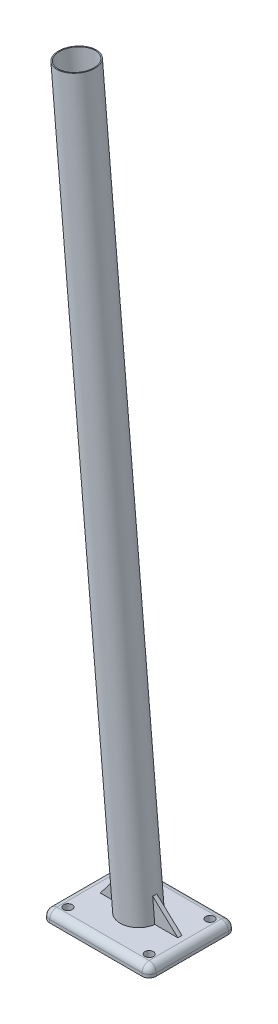
SolidWorks part; units mm, degrees
ref_plane "Front Plane" through (0, 0, 0) normal (0, 0, 1) x (1, 0, 0)
ref_plane "Top Plane" through (0, 0, 0) normal (0, 1, 0) x (1, 0, 0)
ref_plane "Right Plane" through (0, 0, 0) normal (1, 0, 0) x (0, 0, -1)
sketch "Sketch1" plane through (0, 0, 0) normal (0, 1, 0) x (1, 0, 0)
  line L1 (52.5, -42.5) -> (-52.5, -42.5)
  line L2 (52.5, -42.5) -> (52.5, 42.5)
  line L3 (52.5, 42.5) -> (-52.5, 42.5)
  line L4 (-52.5, -42.5) -> (-52.5, 42.5)
  line L5 (52.5, -42.5) -> (-52.5, 42.5) construction
  line L6 (52.5, 42.5) -> (-52.5, -42.5) construction
  line L7 (40, -30) -> (-40, -30) construction
  line L8 (40, -30) -> (40, 30) construction
  line L9 (40, 30) -> (-40, 30) construction
  line L10 (-40, -30) -> (-40, 30) construction
  line L11 (40, -30) -> (-40, 30) construction
  line L12 (40, 30) -> (-40, -30) construction
  circle A2 centre (-40, -30) radius 4.2
  circle A3 centre (40, 30) radius 4.2
  circle A4 centre (40, -30) radius 4.2
  circle A5 centre (-40, 30) radius 4.2
  point P0 (0, 0)
  point P6 (0, 0)
  dimension "D3" = 60
  dimension "D5" = 8.4
  dimension "D1" = 85
  dimension "D2" = 105
  dimension "D4" = 80
extrude "Boss-Extrude1" add sketch "Sketch1" along normal blind 10
sketch "Sketch5" plane through (0, 0, 0) normal (0, 0, 1) x (1, 0, 0)
  line L0 (0, 99.305) -> (0, -31.2001) construction
  line L2 (-7.9994, 101.4331) -> (0, 10)
  line L3 (-52.5, 10) -> (52.5, 10) construction
  dimension "D1" = 85
ref_plane "Plane1" through (0, 10, 0) normal (0.0872, -0.9962, 0) x (-0.9962, -0.0872, 0)
sketch "Sketch14" plane through (0, 10, 0) normal (0.0872, -0.9962, 0) x (-0.9962, -0.0872, 0)
  line L0 (-7.7834, 0) -> (3.5908, 0) construction
  line L1 (-51.4287, -42.5) -> (52.3002, 42.5) construction
  line L2 (-51.4287, 42.5) -> (52.3002, -42.5) construction
  circle A0 centre (0.4358, 0) radius 18
  circle A1 centre (0.4358, 0) radius 17
  dimension "D1" = 36
  dimension "D3" = 0
  dimension "D2" = 34
extrude "Boss-Extrude4" add sketch "Sketch14" against normal blind 700 and the other way up to surface other way up to face at (40, 10, 34.2)
sketch "Sketch16" plane through (0, 0, 0) normal (0, 0, 1) x (1, 0, 0)
  line L0 (36.0762, 10.055) -> (-3.0211, 63.3047)
ref_plane "Plane2" through (-52.5, 10, 42.5) normal (1, 0, 0) x (0, 0, -1)
sketch "Sketch21" plane through (0, 0, 0) normal (0, 0, 1) x (1, 0, 0)
  line L0 (15.616, 33.0356) -> (40.2682, 10)
  line L1 (17.6313, 10) -> (-43.5116, 708.8671) construction
  line L2 (-52.5, 10) -> (52.5, 10) construction
rib "Rib2" sketch "Sketch21" sketch "Sketch21" thickness 4 extrusion direction parallel to sketch draft on no parameters "D1"=4
sketch "Sketch22" plane through (0, 0, 0) normal (0, 0, 1) x (1, 0, 0)
  line L0 (-20.3162, 30.6879) -> (-36.1382, 10)
  line L1 (-79.3746, 705.7295) -> (-18.5062, 10) construction
  line L2 (-52.5, 10) -> (52.5, 10) construction
rib "Rib5" sketch "Sketch22" sketch "Sketch22" thickness 4 extrusion direction parallel to sketch draft on no parameters "D1"=4
fillet "Fillet1" radius 7 4 edges at (52.5, 10, 0) (-52.5, 10, 0) (52.5, 5, 42.5) (-52.5, 5, 42.5)
fillet "Fillet2" radius 7 8 edges at (50.4497, 7.9497, -42.5) (-50.4497, 7.9497, -42.5) (-50.4497, 7.9497, 40.4497) (50.4497, 7.9497, 40.4497) (0, 10, -42.5) (0, 10, 42.5) (52.5, 1.5, -42.5) (-52.5, 1.5, -42.5)
rib "Rib1" [suppressed] sketch "Sketch16" sketch "Sketch16" thickness 10 extrusion direction parallel to sketch draft on no parameters "D1"=10
ref_plane "Plane3" through (-17.4974, -1.5308, 0) normal (-0.9962, -0.0872, 0) x (0, 0, 1)
sketch "Sketch26" plane through (-17.4974, -1.5308, 0) normal (-0.9962, -0.0872, 0) x (0, 0, 1)
  line L0 (17, 709.9619) -> (-17, 709.9619) construction
  line L1 (0, 709.9619) -> (0, 659.9619) construction
  circle A0 centre (0, 659.9619) radius 4.1
  dimension "D2" = 8.2
  dimension "D1" = 50
extrude "Cut-Extrude1" cut sketch "Sketch26" against normal up to next
